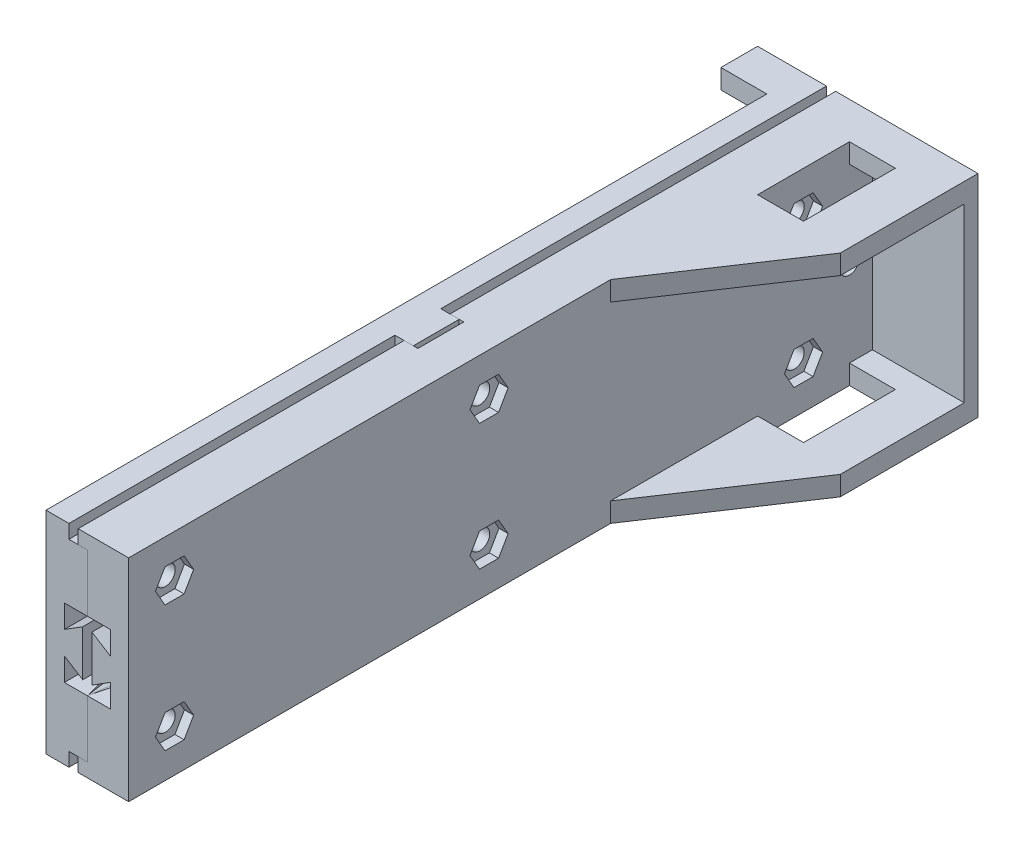
SolidWorks part; units mm, degrees
ref_plane "Front Plane" through (0, 0, 0) normal (0, 0, 1) x (1, 0, 0)
ref_plane "Top Plane" through (0, 0, 0) normal (0, 1, 0) x (1, 0, 0)
ref_plane "Right Plane" through (0, 0, 0) normal (1, 0, 0) x (0, 0, -1)
sketch "Sketch1" plane through (0, 0, 0) normal (1, 0, 0) x (0, 0, -1)
  line L1 (-76, -7.5) -> (76, -7.5)
  line L2 (-76, -7.5) -> (-76, 7.5)
  line L3 (-76, 7.5) -> (76, 7.5)
  line L4 (76, -7.5) -> (76, 7.5)
  line L5 (-76, -7.5) -> (76, 7.5) construction
  line L6 (-76, 7.5) -> (76, -7.5) construction
  point P1 (0, 0)
  dimension "D1" = 152
  dimension "D2" = 15
extrude "Boss-Extrude1" add sketch "Sketch1" along normal mid plane 2
sketch "Sketch2" plane through (1, 0, 0) normal (1, 0, 0) x (0, 0, -1)
  line L0 (-76, -7.5) -> (76, -7.5) construction
  line L1 (76, 7.5) -> (56, 7.5)
  line L2 (76, 7.5) -> (76, -7.5)
  line L3 (76, -7.5) -> (56, -7.5)
  line L4 (56, 7.5) -> (56, -7.5)
  dimension "D1" = 20
extrude "Boss-Extrude2" add sketch "Sketch2" along normal blind 4
sketch "Sketch3" plane through (0, 0, -56) normal (0, 0, 1) x (1, 0, 0)
  line L0 (5, 0) -> (1, 0) construction
  line L1 (5, 7.5) -> (5, -7.5) construction
  line L2 (1, 7.5) -> (1, -7.5) construction
  line L3 (5, 2.5) -> (1, 5)
  line L4 (1, 5) -> (1, -5)
  line L5 (1, -5) -> (5, -2.5)
  line L6 (5, -2.5) -> (5, 2.5)
  dimension "D1" = 5
  dimension "D2" = 10
  dimension "D3" = 4
extrude "Cut-Extrude1" cut sketch "Sketch3" against normal through all
mirror "Mirror1" about plane through (0, 0, 0) normal (1, 0, 0) of "Cut-Extrude1", "Boss-Extrude2"
mirror "Mirror2" about plane through (0, 0, 0) normal (0, 0, 1) of "Mirror1", "Boss-Extrude2", "Cut-Extrude1"
sketch "Sketch7" plane through (0, 7.5, 0) normal (0, 1, 0) x (1, 0, 0)
  line L0 (0, -58.25) -> (0, 49941.75) construction
  line L1 (5, -76) -> (-5, -76) construction
  line L2 (0, -76) -> (-5, -56)
  line L3 (-5, -56) -> (-1, -56) construction
  line L4 (-5, -56) -> (-5, 56)
  line L5 (-5, 56) -> (-1, 56) construction
  line L6 (-5, 56) -> (0, 76)
  line L7 (5, 76) -> (-5, 76) construction
  line L8 (5, 56) -> (0, 76)
  line L9 (5, -56) -> (5, 56)
  line L10 (0, -76) -> (5, -56)
  line L11 (1, 56) -> (1, -56) construction
  point P4 (0, -76)
  dimension "D1" = 4
extrude "Boss-Extrude5" add sketch "Sketch7" along normal blind 2.5
sketch "Sketch8" plane through (-5, 0, 0) normal (-1, 0, 0) x (0, 0, 1)
  line L0 (-56, 10) -> (-76, 7.5)
  line L1 (-76, 7.5) -> (-76, 10)
  line L2 (-76, 10) -> (-56, 10)
  line L3 (0, 9) -> (0, -49991) construction
  line L4 (-56, 10) -> (56, 10) construction
  line L5 (76, 10) -> (56, 10)
  line L6 (76, 7.5) -> (76, 10)
  line L7 (56, 10) -> (76, 7.5)
  point P17 (0, 10)
extrude "Cut-Extrude2" cut sketch "Sketch8" against normal through all
sketch "Sketch9" plane through (0, 0, 76) normal (0, 0, 1) x (1, 0, 0)
  line L0 (0, 7.5) -> (0, -49992.5) construction
  line L1 (5, 7.5) -> (0, 7.5) construction
  circle A0 centre (1.2, 9.7) radius 0.75
  circle A1 centre (-1.2, 9.7) radius 0.75
  dimension "D2" = 1.5
  dimension "D1" = 1.2
  dimension "D3" = 2.2
extrude "Cut-Extrude3" cut sketch "Sketch9" against normal through all
mirror "Mirror4" about plane through (0, 0, 0) normal (0, 1, 0) of "Boss-Extrude5", "Cut-Extrude2", "Cut-Extrude3"
sketch "Sketch10" plane through (0, 0, -76) normal (0, 0, -1) x (-1, 0, 0)
  line L0 (-5, 8.5) -> (-3.2, 10)
  line L1 (-5, 10) -> (-5, 7.5) construction
  line L2 (-5, 10) -> (-1.8874, 10) construction
  line L3 (-3.2, 10) -> (-5, 10)
  line L4 (-5, 10) -> (-5, 8.5)
  line L5 (-5, 7.5) -> (0, 7.5) construction
  line L6 (0, 9) -> (0, -49991) construction
  line L7 (-0.5126, 10) -> (0.5126, 10) construction
  line L8 (0, 0) -> (50000, 0) construction
  line L9 (5, 10) -> (5, 8.5)
  line L10 (3.2, 10) -> (5, 10)
  line L11 (5, 8.5) -> (3.2, 10)
  line L12 (-5, -10) -> (-5, -8.5)
  line L13 (-3.2, -10) -> (-5, -10)
  line L14 (-5, -8.5) -> (-3.2, -10)
  line L15 (5, -8.5) -> (3.2, -10)
  line L16 (3.2, -10) -> (5, -10)
  line L17 (5, -10) -> (5, -8.5)
  arc A0 (-1.8874, 10) -> (-0.5126, 10) centre (-1.2, 9.7) ccw construction
  point P17 (0, 10)
  dimension "D1" = 1
  dimension "D2" = 2
extrude "Cut-Extrude4" cut sketch "Sketch10" against normal through all
sketch "Sketch11" plane through (-5, 0, 0) normal (-1, 0, 0) x (0, 0, 1)
  line L0 (0, 0) -> (50000, 0) construction
  line L1 (-86, 20) -> (76, 20)
  line L2 (-86, 20) -> (-86, -20)
  line L3 (-86, -20) -> (76, -20)
  line L4 (76, 20) -> (76, -20)
  line L5 (-86, 20) -> (76, -20) construction
  line L6 (-86, -20) -> (76, 20) construction
  line L7 (76, 2.5) -> (76, 7.5) construction
  line L11 (56, 10) -> (-56, 10) construction
  line L12 (-76, 2.5) -> (-76, 7.5) construction
  point P9 (-5, 0)
  dimension "D1" = 10
  dimension "D2" = 10
  dimension "D3" = 0
extrude "Boss-Extrude6" add sketch "Sketch11" along normal blind 4 and the other way offset from surface (14 mm away) 4 separate body other way up to face at (5, 5, -66)
combine bodies "Combine1" operation type subtract main body 115 bodies to subtract 114
split "Split1" trim tools "Right Plane" bodies to split 116 resulting bodies 117 118
sketch "Sketch12" plane through (9, 0, 0) normal (1, 0, 0) x (0, 0, -1)
  line L1 (-76, -23) -> (89, -23)
  line L2 (89, -23) -> (89, 23)
  line L3 (89, 23) -> (-76, 23)
  line L4 (-76, 20) -> (-76, -20)
  line L5 (-76, -20) -> (86, -20)
  line L6 (86, -20) -> (86, 20)
  line L7 (86, 20) -> (-76, 20)
  line L9 (-76, -20) -> (86, -20)
  line L10 (86, -20) -> (86, 20)
  line L11 (86, 20) -> (-76, 20)
  line L12 (-76, -20) -> (-76, -23)
  line L13 (-76, 20) -> (-76, 23)
  line L15 (89, 23) -> (-79, 23) construction
  line L16 (-79, 23) -> (-79, -23) construction
  line L17 (-79, -23) -> (89, -23) construction
  line L18 (-76, 20) -> (-76, -20) construction
  dimension "D1" = 0
  dimension "D2" = 3
extrude "Boss-Extrude7" add sketch "Sketch12" against normal offset from surface (11 mm away) 2
sketch "Sketch13" plane through (-9, 0, 0) normal (-1, 0, 0) x (0, 0, 1)
  line L1 (76, 23) -> (-89, 23)
  line L2 (-89, 23) -> (-89, -23)
  line L3 (-89, -23) -> (76, -23)
  line L4 (76, -20) -> (76, 20)
  line L5 (76, 20) -> (-86, 20)
  line L6 (-86, 20) -> (-86, -20)
  line L7 (-86, -20) -> (76, -20)
  line L9 (76, 20) -> (-86, 20)
  line L10 (-86, 20) -> (-86, -20)
  line L11 (-86, -20) -> (76, -20)
  line L12 (76, 23) -> (76, 20)
  line L13 (76, -20) -> (76, -23)
  line L14 (76, -20) -> (76, 20) construction
  line L16 (-89, -23) -> (79, -23) construction
  line L17 (79, -23) -> (79, 23) construction
  line L18 (79, 23) -> (-89, 23) construction
  dimension "D1" = 0
  dimension "D2" = 3
extrude "Boss-Extrude8" add sketch "Sketch13" against normal offset from surface (5 mm away) 4 up to face at (0, 0, -1.6667)
sketch "Sketch14" plane through (-4, 0, 0) normal (1, 0, 0) x (0, 0, -1)
  line L0 (0, 0) -> (0, 50000) construction
  line L3 (0, 0) -> (50000, 0) construction
  line L4 (86, 20) -> (-76, 20) construction
  line L5 (-5, 23) -> (5, 23)
  line L6 (-5, 23) -> (-5, 20)
  line L7 (-5, 20) -> (5, 20)
  line L8 (5, 23) -> (5, 20)
  line L9 (-5, 23) -> (5, 20) construction
  line L10 (-5, 20) -> (5, 23) construction
  line L11 (-76, 23) -> (89, 23) construction
  line L12 (5, -23) -> (5, -20)
  line L13 (-5, -20) -> (5, -20)
  line L14 (-5, -23) -> (-5, -20)
  line L15 (-5, -23) -> (5, -23)
  point P5 (0, 21.5)
  dimension "D1" = 10
extrude "Boss-Extrude9" add sketch "Sketch14" along normal up to surface (4 mm away) up to face at (0, 0, -1.6667)
sketch "Sketch15" plane through (-2, 0, 0) normal (-1, 0, 0) x (0, 0, 1)
  line L0 (0, 0) -> (0, -50000) construction
  line L1 (0, 0) -> (-50000, 0) construction
  line L2 (76, -20) -> (-86, -20) construction
  line L3 (5, -23) -> (-5, -23)
  line L4 (5, -23) -> (5, -20)
  line L5 (5, -20) -> (-5, -20)
  line L6 (-5, -23) -> (-5, -20)
  line L7 (5, -23) -> (-5, -20) construction
  line L8 (5, -20) -> (-5, -23) construction
  line L9 (-89, -23) -> (76, -23) construction
  line L10 (5, 20) -> (-5, 20)
  line L11 (-5, 23) -> (-5, 20)
  line L12 (5, 23) -> (-5, 23)
  line L13 (5, 23) -> (5, 20)
  point P5 (0, -21.5)
  dimension "D1" = 10
extrude "Cut-Extrude5" cut sketch "Sketch15" against normal blind 3
sketch "Sketch16" plane through (-9, 0, 0) normal (-1, 0, 0) x (0, 0, 1)
  line L0 (76, -20) -> (76, -7.5) construction
  line L1 (76, -20) -> (76, -7.5) construction
  line L2 (58.25, -13.75) -> (-49941.75, -13.75) construction
  line L3 (0, 0) -> (50000, 0) construction
  line L4 (-76, -7.5) -> (-76, 7.5) construction
  line L5 (-76, -7.5) -> (-76, 7.5) construction
  line L6 (-86, 20) -> (-86, -20) construction
  line L7 (-86, 20) -> (-86, -20) construction
  line L8 (-76, -7.5) -> (-86, -7.5) construction
  line L9 (-81, -7.5) -> (-81, 49992.5) construction
  line L11 (-71, -13.75) -> (-71, -19) construction
  line L12 (-71, -19) -> (-2.5, -19) construction
  line L13 (-2.5, -19) -> (-2.5, -13.75) construction
  line L14 (-2.5, -19) -> (66, -19) construction
  line L15 (66, -19) -> (66, -13.75) construction
  line L16 (76, -23) -> (76, 23) construction
  circle A0 centre (-81, 0) radius 2.15
  circle A1 centre (66, -13.75) radius 2.15
  circle A2 centre (-71, -13.75) radius 2.15
  circle A3 centre (-2.5, -13.75) radius 2.15
  circle A4 centre (-71, 13.75) radius 2.15
  circle A5 centre (-2.5, 13.75) radius 2.15
  circle A6 centre (66, 13.75) radius 2.15
  point P4 (76, -13.75)
  point P15 (-81, -7.5)
  dimension "D1" = 4.3
  dimension "D2" = 10
  dimension "D3" = 10
extrude "Cut-Extrude6" cut sketch "Sketch16" against normal through all
sketch "Sketch18" plane through (-1, 0, 0) normal (1, 0, 0) x (0, 0, -1)
  line L0 (76, 0) -> (71, 0) construction
  line L1 (76, 5) -> (76, -5) construction
  circle A0 centre (71, 0) radius 1
  dimension "D1" = 2
  dimension "D2" = 5
extrude "Cut-Extrude7" cut sketch "Sketch18" against normal through all
sketch "Sketch19" plane through (-9, 0, 0) normal (-1, 0, 0) x (0, 0, 1)
  circle A0 centre (-71, 0) radius 1 construction
  circle A1 centre (-71, 0) radius 1
  circle A2 centre (-71, 0) radius 3.5
  dimension "D1" = 7
extrude "Cut-Extrude8" cut sketch "Sketch19" against normal blind 2
sketch "Sketch20" plane through (-9, 0, 0) normal (-1, 0, 0) x (0, 0, 1)
  circle A0 centre (-71, 0) radius 3.5 construction
  circle A1 centre (-71, 0) radius 3.5
  circle A2 centre (-71, 0) radius 5.5
  dimension "D1" = 2
extrude "Boss-Extrude10" add sketch "Sketch20" along normal blind 2
sketch "Sketch22" plane through (9, 0, 0) normal (1, 0, 0) x (0, 0, -1)
  line L0 (0, 0) -> (50000, 0) construction
  line L1 (29, -23) -> (29, -18.75)
  line L2 (-76, -23) -> (89, -23) construction
  line L3 (29, -18.75) -> (86, -18.75)
  line L4 (86, -18.75) -> (86, 18.75)
  line L7 (89, 23) -> (89, -23)
  line L8 (89, -23) -> (29, -23)
  line L9 (29, 18.75) -> (86, 18.75)
  line L10 (29, 23) -> (29, 18.75)
  line L11 (89, 23) -> (29, 23)
  circle A0 centre (71, 13.75) radius 2.15 construction
  circle A1 centre (81, 0) radius 2.15 construction
  dimension "D1" = 5
  dimension "D2" = 5
  dimension "D3" = 60
extrude "Boss-Extrude11" add sketch "Sketch22" along normal blind 20
sketch "Sketch23" plane through (0, -23, 0) normal (0, -1, 0) x (1, 0, 0)
  line L0 (9, -29) -> (29, -29)
  line L1 (29, -29) -> (29, -59)
  line L3 (29, -59) -> (9, -29)
  line L4 (29, -86) -> (29, -29) construction
  line L5 (29, -59) -> (29, -29)
  line L6 (29, -29) -> (29, -89) construction
  line M7 (29, -89) -> (29, -29)
  line M8 (29, -29) -> (9, -29)
  dimension "D1" = 30
extrude "Cut-Extrude9" cut sketch "Sketch23" against normal through all contours L3 M7 M8
sketch "Sketch24" plane through (9, 0, 0) normal (1, 0, 0) x (0, 0, -1)
  line L0 (0, 0) -> (50000, 0) construction
  line L1 (71, 12.2434) -> (71, -49987.7566) construction
  line L2 (89, 23) -> (59, 23) construction
  line L3 (81, -23) -> (61, -23)
  line L4 (81, -23) -> (81, 23)
  line L5 (81, 23) -> (61, 23)
  line L6 (61, -23) -> (61, 23)
  line L7 (81, -23) -> (61, 23) construction
  line L8 (81, 23) -> (61, -23) construction
  point P2 (71, 0)
  dimension "D1" = 20
extrude "Cut-Extrude10" cut sketch "Sketch24" along normal blind 10
sketch "Sketch25" plane through (9, 0, 0) normal (1, 0, 0) x (0, 0, -1)
  line L0 (86, -18.75) -> (59, -18.75) construction
  line L1 (73.0785, -10.15) -> (68.9215, -10.15)
  line L2 (68.9215, -10.15) -> (66.8431, -13.75)
  line L3 (66.8431, -13.75) -> (68.9215, -17.35)
  line L4 (68.9215, -17.35) -> (73.0785, -17.35)
  line L5 (73.0785, -17.35) -> (75.1569, -13.75)
  line L6 (75.1569, -13.75) -> (73.0785, -10.15)
  line L7 (63.25, 0) -> (-49936.75, 0) construction
  line L8 (4.5785, -10.15) -> (0.4215, -10.15)
  line L9 (0.4215, -10.15) -> (-1.6569, -13.75)
  line L10 (-1.6569, -13.75) -> (0.4215, -17.35)
  line L11 (0.4215, -17.35) -> (4.5785, -17.35)
  line L12 (4.5785, -17.35) -> (6.6569, -13.75)
  line L13 (6.6569, -13.75) -> (4.5785, -10.15)
  line L14 (-63.9215, -10.15) -> (-68.0785, -10.15)
  line L15 (-68.0785, -10.15) -> (-70.1569, -13.75)
  line L16 (-70.1569, -13.75) -> (-68.0785, -17.35)
  line L17 (-68.0785, -17.35) -> (-63.9215, -17.35)
  line L18 (-63.9215, -17.35) -> (-61.8431, -13.75)
  line L19 (-61.8431, -13.75) -> (-63.9215, -10.15)
  line L20 (4.5785, 17.35) -> (0.4215, 17.35)
  line L21 (0.4215, 17.35) -> (-1.6569, 13.75)
  line L22 (-1.6569, 13.75) -> (0.4215, 10.15)
  line L23 (0.4215, 10.15) -> (4.5785, 10.15)
  line L24 (4.5785, 10.15) -> (6.6569, 13.75)
  line L25 (6.6569, 13.75) -> (4.5785, 17.35)
  line L26 (-63.9215, 17.35) -> (-68.0785, 17.35)
  line L27 (-68.0785, 17.35) -> (-70.1569, 13.75)
  line L28 (-70.1569, 13.75) -> (-68.0785, 10.15)
  line L29 (-68.0785, 10.15) -> (-63.9215, 10.15)
  line L30 (-63.9215, 10.15) -> (-61.8431, 13.75)
  line L31 (-61.8431, 13.75) -> (-63.9215, 17.35)
  line L32 (73.0785, 17.35) -> (68.9215, 17.35)
  line L33 (68.9215, 17.35) -> (66.8431, 13.75)
  line L34 (66.8431, 13.75) -> (68.9215, 10.15)
  line L35 (68.9215, 10.15) -> (73.0785, 10.15)
  line L36 (73.0785, 10.15) -> (75.1569, 13.75)
  line L37 (75.1569, 13.75) -> (73.0785, 17.35)
  circle A0 centre (71, -13.75) radius 3.6 construction
  circle A1 centre (71, 13.75) radius 3.6 construction
  circle A2 centre (71, 13.75) radius 2.15 construction
  circle A3 centre (-66, -13.75) radius 3.6 construction
  dimension "D1" = 7.2
  dimension "D2" = 3
  dimension "D3" = 2
extrude "Cut-Extrude11" cut sketch "Sketch25" against normal blind 2
sketch "Sketch26" plane through (-9, 0, 0) normal (-1, 0, 0) x (0, 0, 1)
  line L0 (0, 0) -> (-50000, 0) construction
  line L1 (-89, 23) -> (-81, 23)
  line L2 (-89, 23) -> (-89, 18.75)
  line L3 (-89, 18.75) -> (-81, 18.75)
  line L4 (-81, 23) -> (-81, 18.75)
  line L5 (-81, -23) -> (-81, -18.75)
  line L6 (-89, -18.75) -> (-81, -18.75)
  line L7 (-89, -23) -> (-89, -18.75)
  line L8 (-89, -23) -> (-81, -23)
  line L9 (-81, 18.75) -> (-81, 23) construction
  line L10 (-81, 18.75) -> (-81, 23) construction
extrude "Boss-Extrude12" add sketch "Sketch26" along normal blind 10
